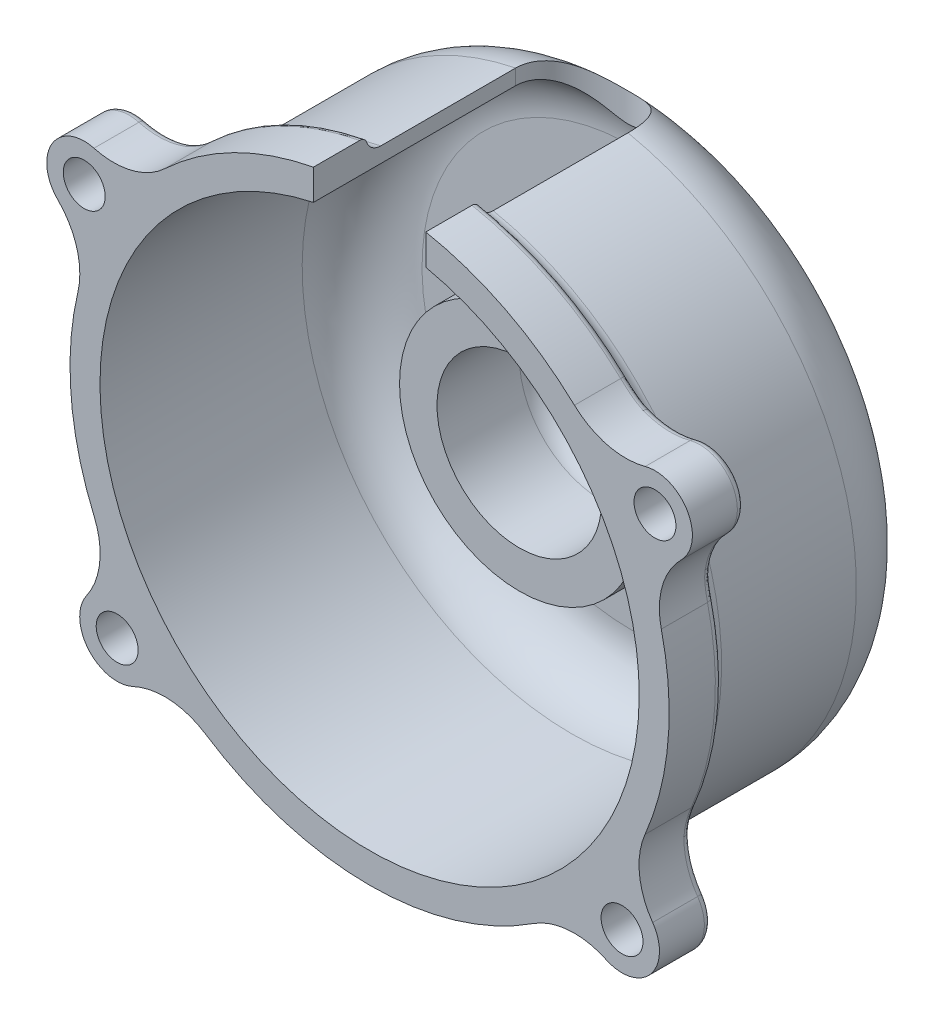
SolidWorks part; units mm, degrees
ref_plane "Спереди" through (0, 0, 0) normal (0, 0, 1) x (1, 0, 0)
ref_plane "Сверху" through (0, 0, 0) normal (0, 1, 0) x (1, 0, 0)
ref_plane "Справа" through (0, 0, 0) normal (1, 0, 0) x (0, 0, -1)
sketch "Эскиз1" plane through (0, 0, 0) normal (0, 0, 1) x (1, 0, 0)
  line L0 (0, 0) -> (0, -20) construction
  line L1 (0, 0) -> (16.853, -14.1413) construction
  line L2 (0, 0) -> (-20, 0) construction
  line L3 (0, 0) -> (19.0526, 11) construction
  arc A0 (16.2004, -11.728) -> (17.9909, 8.7366) centre (0, 0) ccw
  arc A1 (-14.363, -13.9178) -> (-16.2004, -11.728) centre (-16.853, -14.1413) cw
  circle A2 centre (-16.853, -14.1413) radius 1.4
  circle A3 centre (16.853, -14.1413) radius 1.4
  arc A4 (14.363, -13.9178) -> (16.2004, -11.728) centre (16.853, -14.1413) ccw
  arc A5 (-14.363, -13.9178) -> (14.363, -13.9178) centre (0, 0) ccw
  circle A6 centre (16.853, -14.1413) radius 2 construction
  circle A7 centre (-19.0526, 11) radius 1.4
  arc A8 (16.5616, 11.2122) -> (17.9909, 8.7366) centre (19.0526, 11) cw
  circle A9 centre (0, 0) radius 22 construction
  circle A10 centre (19.0526, 11) radius 1.4
  arc A11 (-16.5616, 11.2122) -> (-17.9909, 8.7366) centre (-19.0526, 11) ccw
  arc A13 (-17.9909, 8.7366) -> (-16.2004, -11.728) centre (0, 0) ccw
  arc A14 (16.5616, 11.2122) -> (-16.5616, 11.2122) centre (0, 0) ccw
  point P14 (0, 0)
  point P17 (0, 0)
  dimension "D1" = 20
  dimension "D2" = 44
  dimension "D3" = 2.5
  dimension "D5" = 2.8
  dimension "D6" = 4
  dimension "D4" = 50
  dimension "D7" = 120
extrude "основание" add sketch "Эскиз1" along normal blind 3.5
fillet "Скругления наплывов" radius 5 8 edges at (14.363, -13.9178, 1.75) (16.2004, -11.728, 1.75) (-14.363, -13.9178, 1.75) (17.9909, 8.7366, 1.75) (16.5616, 11.2122, 1.75) (-16.2004, -11.728, 1.75) (-16.5616, 11.2122, 1.75) (-17.9909, 8.7366, 1.75)
sketch "Эскиз2" plane through (0, 0, 0) normal (0, 0, -1) x (-1, 0, 0)
  circle A0 centre (0, 0) radius 19
extrude "место для энкодера" [suppressed] add sketch "Эскиз2" along normal blind 14
sketch "Эскиз3" plane through (0, 0, 3.5) normal (0, 0, 1) x (1, 0, 0)
  circle A0 centre (0, 0) radius 18
  dimension "D1" = 36
extrude "углубление для двигателя" [suppressed] cut sketch "Эскиз3" against normal blind 14
chamfer "Фаска1" [suppressed] distance 1 distance2 20
fillet "Скругление4" [suppressed] radius 5
fillet "Скругление5" [suppressed] radius 2
extrude "Место под выступ двигателя с проводами" add sketch "Эскиз2<2>" along normal blind 15
sketch "Эскиз2<2>" plane through (0, 0, 0) normal (0, 0, -1) x (-1, 0, 0) same geometry as "Эскиз2"
fillet "Скругление10" radius 5 1 edges at (-19, 0, -15)
fillet "Скругление11" radius 1 1 edges at (-19, 0, 0)
fillet "Скругление12" radius 0.5 16 edges at (19.9239, -1.7431, 0) (18.015, -10.3483, 0) (18.7681, -15.7483, 0) (13.3193, -15.9443, 0) (0, -20, 0) (-13.3193, -15.9443, 0) (-18.7681, -15.7483, 0) (-18.015, -10.3483, 0) (-19.9239, -1.7431, 0) (0, 20, 0) (15.8857, 13.3892, 0) (21.2176, 12.25, 0) (19.5382, 7.0628, 0) (-19.5382, 7.0628, 0) (-21.2176, 12.25, 0) (-15.8857, 13.3892, 0)
sketch "Эскиз14" plane through (0, 0, 0) normal (1, 0, 0) x (0, 0, -1)
  line L0 (-3.5, 18) -> (10, 18)
  line L1 (-3.5, 4.5486) -> (-3.5, -7.8614) construction
  line L2 (14, 14) -> (14, 0)
  line L3 (-3.5, 18) -> (-3.5, 0)
  line L4 (-3.5, 0) -> (0, 0) construction
  line L5 (14, 0) -> (-3.5, 0)
  arc A0 (14, 14) -> (10, 18) centre (10, 14) ccw
  arc A1 (15, 14) -> (10, 19) centre (10, 14) ccw construction
  dimension "D1" = 18
revolve "Углубление под двигатель jgb37_3525" cut sketch "Эскиз14" angle 360 about L4
sketch "Эскиз12" plane through (0, 0, -14) normal (0, 0, -1) x (-1, 0, 0)
  circle A0 centre (0, 0) radius 5.5
  circle A1 centre (0, 0) radius 8
  dimension "D1" = 11
  dimension "D2" = 2.5
extrude "защита проводов от вращающегося вала" add sketch "Эскиз12" against normal offset from surface (7.5 mm away) 10 up to face at (0, -18, 3.5)
ref_plane "Плоскость под пазпод провода для защиты 3525" through (0, 0, 0) normal (0, 1, 0) x (1, 0, 0)
sketch "Эскиз13" plane through (0, 0, 0) normal (0, 1, 0) x (1, 0, 0)
  line L0 (3.75, 10) -> (3.75, -3.5)
  line L1 (0, -50) -> (0, 50) construction
  line L2 (0, 10) -> (0, -6) construction
  line L3 (-3.75, 10) -> (-3.75, -3.5)
  line L9 (3.75, -3.5) -> (-3.75, -3.5)
  line L11 (18.3902, -3.5) -> (20, -3.5) construction
  line L12 (14, 15) -> (-14, 15) construction
  arc A0 (3.75, 10) -> (-3.75, 10) centre (0, 10) ccw
  dimension "D1" = 3.75
  dimension "D2" = 5
extrude "Паз под провода двигателя jgb37_3525" cut sketch "Эскиз13" along normal up to next from offset 15
sketch "Эскиз15" plane through (0, 0, 0) normal (0, 0, -1) x (-1, 0, 0)
  circle A0 centre (-19.0526, 11) radius 2
  circle A1 centre (-16.853, -14.1413) radius 2
  circle A2 centre (16.853, -14.1413) radius 2
  circle A3 centre (19.0526, 11) radius 2
  dimension "D1" = 4
extrude "Углубления под шляпки шурупов М2" [suppressed] cut sketch "Эскиз15" against normal blind 2
fillet "Скругление13" radius 2 2 edges at (-5.5, 0, -14) (0, -8, -14)
